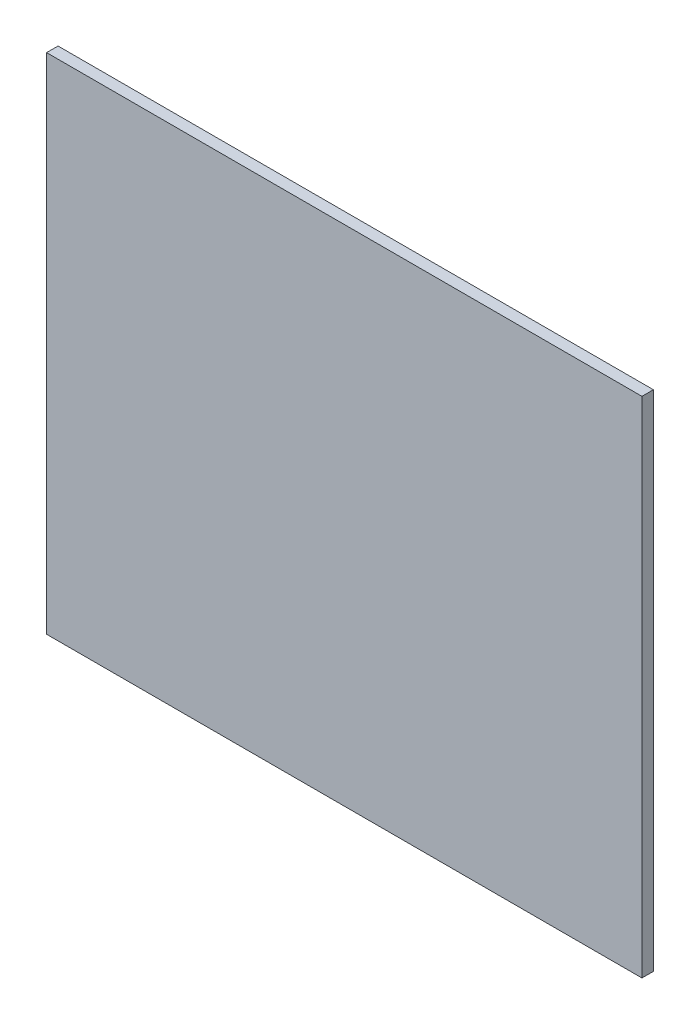
SolidWorks part; units mm, degrees
material "ALUMINUM 6061-T6"
ref_plane "Front Plane" through (0, 0, 0) normal (0, 0, 1) x (1, 0, 0)
ref_plane "Top Plane" through (0, 0, 0) normal (0, 1, 0) x (1, 0, 0)
ref_plane "Right Plane" through (0, 0, 0) normal (1, 0, 0) x (0, 0, -1)
sketch "Sketch1" plane through (0, 0, 0) normal (0, 0, 1) x (1, 0, 0)
  line L1 (-165.1, -139.7) -> (165.1, -139.7)
  line L2 (-165.1, -139.7) -> (-165.1, 139.7)
  line L3 (-165.1, 139.7) -> (165.1, 139.7)
  line L4 (165.1, -139.7) -> (165.1, 139.7)
  line L5 (-165.1, -139.7) -> (165.1, 139.7) construction
  line L6 (-165.1, 139.7) -> (165.1, -139.7) construction
  point P0 (0, 0)
  dimension "D1" = 330.2
  dimension "D2" = 279.4
extrude "Boss-Extrude1" add sketch "Sketch1" along normal mid plane 6.35
